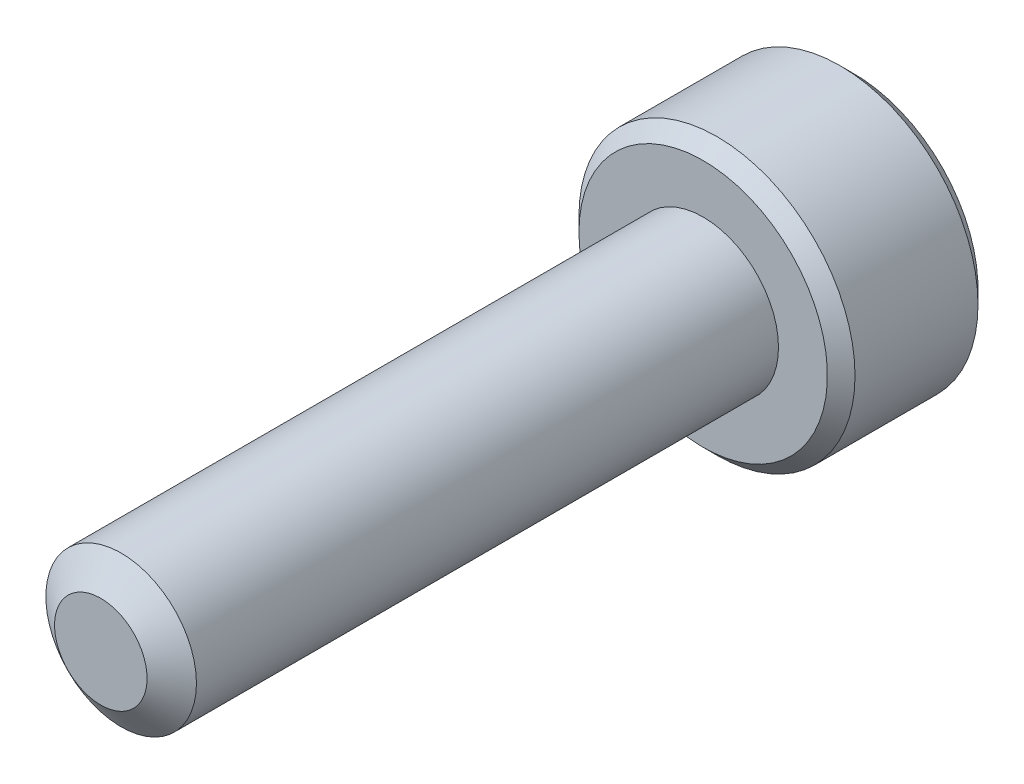
SolidWorks part; units mm, degrees
other "DetailItem1"
material "1.4310 (X10CrNi18-8)"
ref_plane "Front Plane" through (0, 0, 0) normal (0, 0, 1) x (1, 0, 0)
ref_plane "Top Plane" through (0, 0, 0) normal (0, 1, 0) x (1, 0, 0)
ref_plane "Right Plane" through (0, 0, 0) normal (1, 0, 0) x (0, 0, -1)
sketch "Sketch1" plane through (0, 0, 0) normal (0, 0, 1) x (1, 0, 0)
  circle A0 centre (0, 0) radius 1.5
  dimension "OD" = 3
extrude "Extrude1" add sketch "Sketch1" against normal blind 12
sketch "Sketch2" plane through (0, 0, 0) normal (0, 0, 1) x (1, 0, 0)
  circle A0 centre (0, 0) radius 1.5 construction
  circle A1 centre (0, 0) radius 1.5
curve "Helix/Spiral1" pitch 0.5 height 12.5 turns 25 parameters "pitch"=0.5
sketch "Sketch3" plane through (0, 0, 0) normal (1, 0, 0) x (0, 0, -1)
  line L0 (-0.4375, 1.5) -> (-0.25, 1.1752)
  line L1 (-0.25, 1.1752) -> (-0.1875, 1.1752)
  line L2 (-0.1875, 1.1752) -> (0, 1.5)
  line L3 (-0.4375, 1.5) -> (0, 1.5)
  line L4 (-0.2187, 1.5) -> (-0.2188, 1.1752) construction
  line L5 (-0.3438, 1.3376) -> (-0.0938, 1.3376) construction
  line L6 (0, 1.5) -> (0, -1.5) construction
  dimension "D1" = 0.0625
  dimension "D2" = 0.25
  dimension "D3" = 60
sweep "Cut-Sweep1" [suppressed] cut profiles "Sketch3" path "Helix/Spiral1"
sketch "Sketch4" plane through (0, 0, 0) normal (1, 0, 0) x (0, 0, -1)
  line L0 (0.4053, 1.5) -> (0, 0.9212)
  line L1 (0, 0.9212) -> (0, 1.5)
  line L2 (0.4053, 1.5) -> (0, 1.5)
  line L3 (-0.4375, 1.5) -> (0, 1.5) construction
  line L4 (0, 0) -> (7.0209, 0) construction
  dimension "D1" = 55
  dimension "D2" = 0.254
revolve "Cut-Revolve1" cut sketch "Sketch4" angle 360 about L4
sketch "Sketch6" plane through (0, 0, -12) normal (0, 0, -1) x (-1, 0, 0)
  circle A0 centre (0, 0) radius 2.75
  dimension "head dia" = 5.5
extrude "Extrude2" add sketch "Sketch6" along normal blind 3
sketch "Sketch7" plane through (0, 0, -15) normal (0, 0, -1) x (-1, 0, 0)
  line L1 (0, 1.4434) -> (-1.25, 0.7217)
  line L2 (-1.25, 0.7217) -> (-1.25, -0.7217)
  line L3 (-1.25, -0.7217) -> (0, -1.4434)
  line L4 (0, -1.4434) -> (1.25, -0.7217)
  line L5 (1.25, -0.7217) -> (1.25, 0.7217)
  line L6 (1.25, 0.7217) -> (0, 1.4434)
  circle A0 centre (0, 0) radius 1.25 construction
  dimension "hex dia" = 2.5
extrude "Cut-Extrude1" cut sketch "Sketch7" against normal blind 1.875
sketch "Sketch8" plane through (0, 0, -15) normal (0, 0, -1) x (-1, 0, 0)
  circle A0 centre (0, 0) radius 1.4434
extrude "Cut-Extrude2" cut sketch "Sketch8" against normal through all draft 45
chamfer "Chamfer1" distance 0.275 angle 45 2 edges at (-2.75, 0, -15) (-2.75, 0, -12)
sketch "Sketch10" plane through (0, 0, -12) normal (0, 0, 1) x (1, 0, 0)
  circle A1 centre (0, 0) radius 1.5
  circle A2 centre (0, 0) radius 1.5
  dimension "D1" = 0
ref_plane "Plane1" through (0, 0, 0) normal (0, 0, 1) x (1, 0, 0)
extrude "partial thread" [suppressed] add sketch "Sketch10" along normal up to surface (4 mm away) separate body up to plane "Plane1"
chamfer "Chamfer2" [suppressed] distance 0.06 angle 45
combine bodies "Combine1" [suppressed] operation type add bodies to combine 107 108
sketch "Sketch9" plane through (0, 0, 0) normal (1, 0, 0) x (0, 0, -1)
  line L0 (0, 1.5) -> (0, -1.5) construction
  line L1 (1.25, 1.5) -> (1.25, -1.5) construction
  dimension "D1" = 1.25
equation "\"D3@Helix/Spiral1\" = \"screw length@Extrude1\"+\"pitch@Helix/Spiral1\""
equation "\"D1@Sketch3\" = \"pitch@Helix/Spiral1\"*.125"
equation "\"D2@Sketch3\" = \"pitch@Helix/Spiral1\"*.5"
equation "\"D1@Cut-Extrude1\" = \"hex dia@Sketch7\"*.75"
equation "\"D1@Chamfer1\" = \"head dia@Sketch6\"*.05"
equation "\"D1@Sketch9\" = \"pitch@Helix/Spiral1\"*2.5"
equation "\"D1@Chamfer2\"=\"OD@Sketch1\"*.02"
